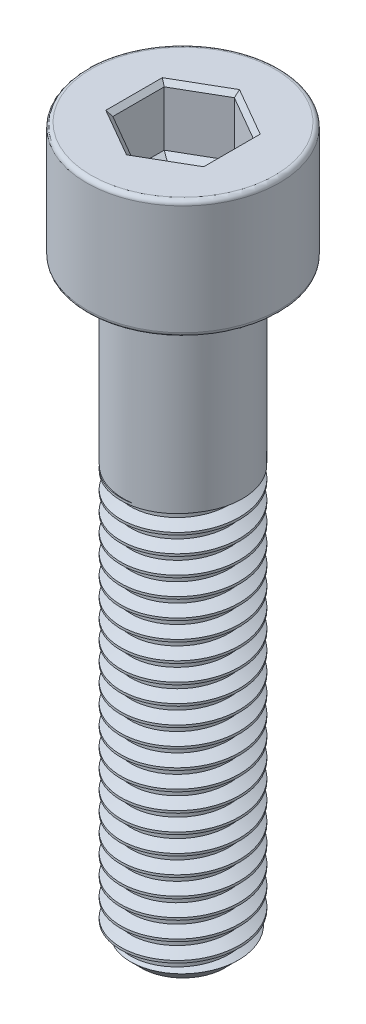
SolidWorks part; units mm, degrees
material "AISI Type A2 Tool Steel"
ref_plane "Front Plane" through (0, 0, 0) normal (0, 0, 1) x (1, 0, 0)
ref_plane "Top Plane" through (0, 0, 0) normal (0, 1, 0) x (1, 0, 0)
ref_plane "Right Plane" through (0, 0, 0) normal (1, 0, 0) x (0, 0, -1)
sketch "Sketch1" plane through (0, 0, 0) normal (0, 1, 0) x (1, 0, 0)
  circle A0 centre (0, 0) radius 4
  dimension "D1" = 8
extrude "Boss-Extrude1" add sketch "Sketch1" along normal blind 28
thread "Thread1" pitch 1.25 method cut profile "Thread Profile1" start angle 0, offset 2, length 0, pitch 1.25, diameter 8
ref_plane "Plane1" through (-4, 30, 0) normal (0, 0, 1) x (-1, 0, 0)
sketch "Thread Profile1" plane through (-4, 30, 0) normal (0, 0, 1) x (-1, 0, 0)
  line L0 (0, 0) -> (0, 1.25) construction
  line L11 (0, 0) -> (0, 1.0937)
  line L12 (0, 1.0937) -> (-0.6766, 0.7031)
  line L13 (-0.6766, 0.7031) -> (-0.6766, 0.3906)
  line L15 (-0.6766, 0.3906) -> (0, 0)
  line L17 (-0.6766, 0.5469) -> (0, 0.5469) construction
  point P2 (0, 0)
  dimension "Pitch" = 1.25
  dimension "Profile_Angle" = 60
  dimension "Profile_Land" = 0.3125
  dimension "Profile_Height" = 0.6766
sketch "Sketch2" plane through (0, 28, 0) normal (0, 1, 0) x (1, 0, 0)
  circle A0 centre (0, 0) radius 4
  dimension "D1" = 8
extrude "Boss-Extrude2" add sketch "Sketch2" along normal blind 12
sketch "Sketch5" plane through (0, 40, 0) normal (0, 1, 0) x (1, 0, 0)
  circle A0 centre (0, 0) radius 6.5
  dimension "D1" = 13
extrude "Boss-Extrude3" add sketch "Sketch5" along normal blind 8
sketch "Sketch6" plane through (0, 0, 0) normal (0, 0, 1) x (1, 0, 0)
  line L0 (0, 0) -> (0, 0.7245) construction
  line L1 (0, 0) -> (4.01, 0) construction
  line L2 (4.01, 0) -> (4.01, 1.2)
  line L3 (4.01, 1.2) -> (2.81, 0)
  line L4 (2.81, 0) -> (4.01, 0)
  dimension "D1" = 1.2
  dimension "D2" = 45
  dimension "D3" = 4.01
revolve "Cut-Revolve1" cut sketch "Sketch6" angle 360 about L0
fillet "Fillet1" radius 0.3 2 edges at (0, 40, 6.5) (0, 48, 6.5)
sketch "Sketch7" plane through (0, 48, 0) normal (0, 1, 0) x (1, 0, 0)
  line L1 (0, 3.4641) -> (-3, 1.7321)
  line L2 (-3, 1.7321) -> (-3, -1.7321)
  line L3 (-3, -1.7321) -> (0, -3.4641)
  line L4 (0, -3.4641) -> (3, -1.7321)
  line L5 (3, -1.7321) -> (3, 1.7321)
  line L6 (3, 1.7321) -> (0, 3.4641)
  circle A0 centre (0, 0) radius 3 construction
  dimension "D1" = 6
extrude "Cut-Extrude1" cut sketch "Sketch7" against normal blind 4
chamfer "Chamfer1" distance 0.3 angle 45 6 edges at (-3, 48, 0) (-1.5, 48, 2.5981) (1.5, 48, 2.5981) (3, 48, 0) (1.5, 48, -2.5981) (-1.5, 48, -2.5981)
sketch "Sketch8" plane through (0, 44, 0) normal (0, 1, 0) x (1, 0, 0)
  line L1 (0, 3.4641) -> (-3, 1.7321)
  line L2 (-3, 1.7321) -> (-3, -1.7321)
  line L3 (-3, -1.7321) -> (0, -3.4641)
  line L4 (0, -3.4641) -> (3, -1.7321)
  line L5 (3, -1.7321) -> (3, 1.7321)
  line L6 (3, 1.7321) -> (0, 3.4641)
  circle A0 centre (0, 0) radius 3 construction
extrude "Cut-Extrude2" cut sketch "Sketch8" against normal blind 0.4 draft 60
